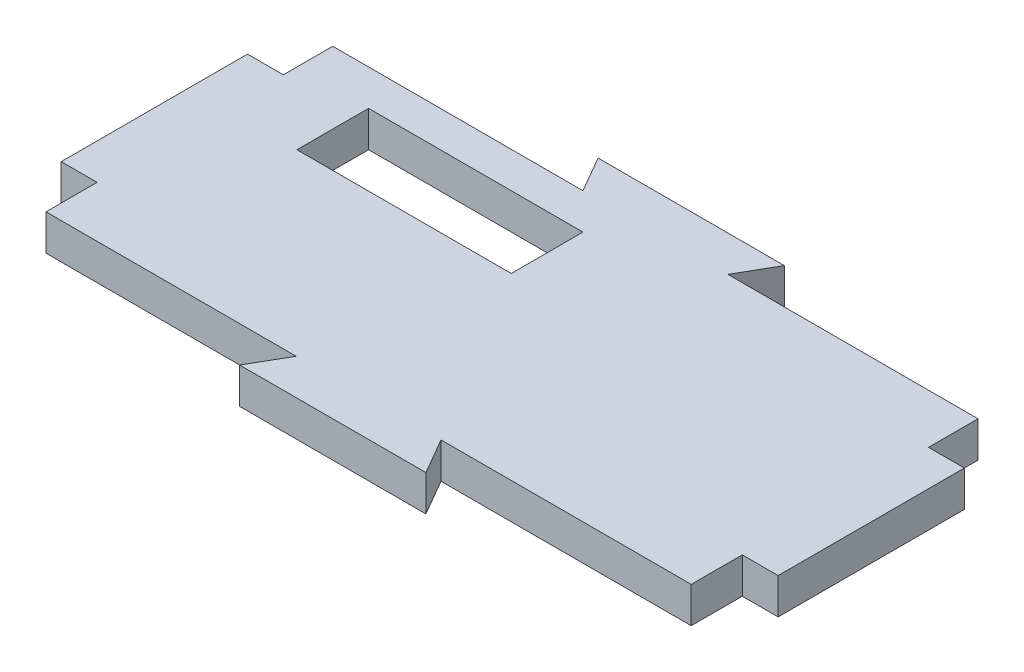
SolidWorks part; units mm, degrees
ref_plane "Front Plane" through (0, 0, 0) normal (1, 0, 0) x (0, 1, 0)
ref_plane "Top Plane" through (0, 0, 0) normal (0, 0, 1) x (0, 1, 0)
ref_plane "Right Plane" through (0, 0, 0) normal (0, 1, 0) x (-1, 0, 0)
sketch "Sketch2" plane through (0, 0, 0) normal (0, 1, 0) x (-1, 0, 0)
  line L1 (-45, -20) -> (45, -20)
  line L2 (-45, -20) -> (-45, 20)
  line L3 (-45, 20) -> (45, 20)
  line L4 (45, -20) -> (45, 20)
  line L5 (-45, -20) -> (45, 20) construction
  line L6 (-45, 20) -> (45, -20) construction
  line L9 (0, 55) -> (0, -55) construction
  line L13 (12.9904, 25) -> (-12.9904, 25)
  line L14 (-12.9904, 25) -> (0, 2.5)
  line L15 (0, 2.5) -> (12.9904, 25)
  line L16 (55, 0) -> (-55, 0) construction
  line L17 (0, -2.5) -> (12.9904, -25)
  line L18 (-12.9904, -25) -> (0, -2.5)
  line L19 (12.9904, -25) -> (-12.9904, -25)
  line L20 (45, -13.1038) -> (50, -13.1038)
  line L21 (-45, 12.877) -> (-50, 12.877)
  line L22 (-45, 12.877) -> (-45, -13.1038)
  line L23 (-45, -13.1038) -> (-50, -13.1038)
  line L24 (-50, 12.877) -> (-50, -13.1038)
  line L25 (50, 12.877) -> (50, -13.1038)
  line L26 (45, 12.877) -> (50, 12.877)
  line L27 (45, 12.877) -> (45, -13.1038)
  circle A2 centre (0, 17.5) radius 7.5
  circle A3 centre (0, -17.5) radius 7.5
  point P0 (0, 0)
  dimension "D6" = 15
  dimension "D1" = 40
  dimension "D2" = 90
  dimension "D3" = 5
  dimension "D7" = 45
  dimension "D8" = 5
extrude "Boss-Extrude1" add sketch "Sketch2" along normal blind 5 contours L25 L4 L3 L2 L1 | L4 | L25 | L25 L20 L27 L26 | L13 L14 L15 | L17 L19 L18 | L22 L21 L24 L23 region at (0, 0, 0)
sketch "Sketch3" plane through (0, 5, 0) normal (0, 1, 0) x (-1, 0, 0)
  line L0 (10.1036, -20) -> (45, -20) construction
  line L1 (35, -15) -> (5.1036, -15)
  line L2 (35, -15) -> (35, -5)
  line L3 (35, -5) -> (5.1036, -5)
  line L4 (5.1036, -15) -> (5.1036, -5)
  line L5 (45, -20) -> (45, -13.1038) construction
  dimension "D1" = 5
  dimension "D2" = 10
  dimension "D3" = 10
  dimension "D4" = 5
extrude "Cut-Extrude1" cut sketch "Sketch3" against normal through all both and the other way through all
